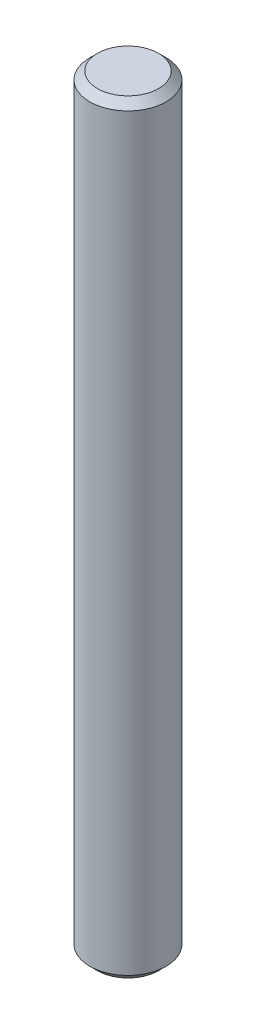
SolidWorks part; units mm, degrees
ref_plane "Front Plane" through (0, 0, 0) normal (0, 0, 1) x (1, 0, 0)
ref_plane "Top Plane" through (0, 0, 0) normal (0, 1, 0) x (1, 0, 0)
ref_plane "Right Plane" through (0, 0, 0) normal (1, 0, 0) x (0, 0, -1)
sketch "Sketch1" plane through (0, 0, 0) normal (0, 1, 0) x (1, 0, 0)
  circle A0 centre (0, 0) radius 2.5
  dimension "D1" = 5
extrude "Boss-Extrude1" add sketch "Sketch1" along normal blind 50
chamfer "Chamfer1" distance 0.5 angle 45 2 edges at (0, 50, 2.5) (0, 0, 2.5)
